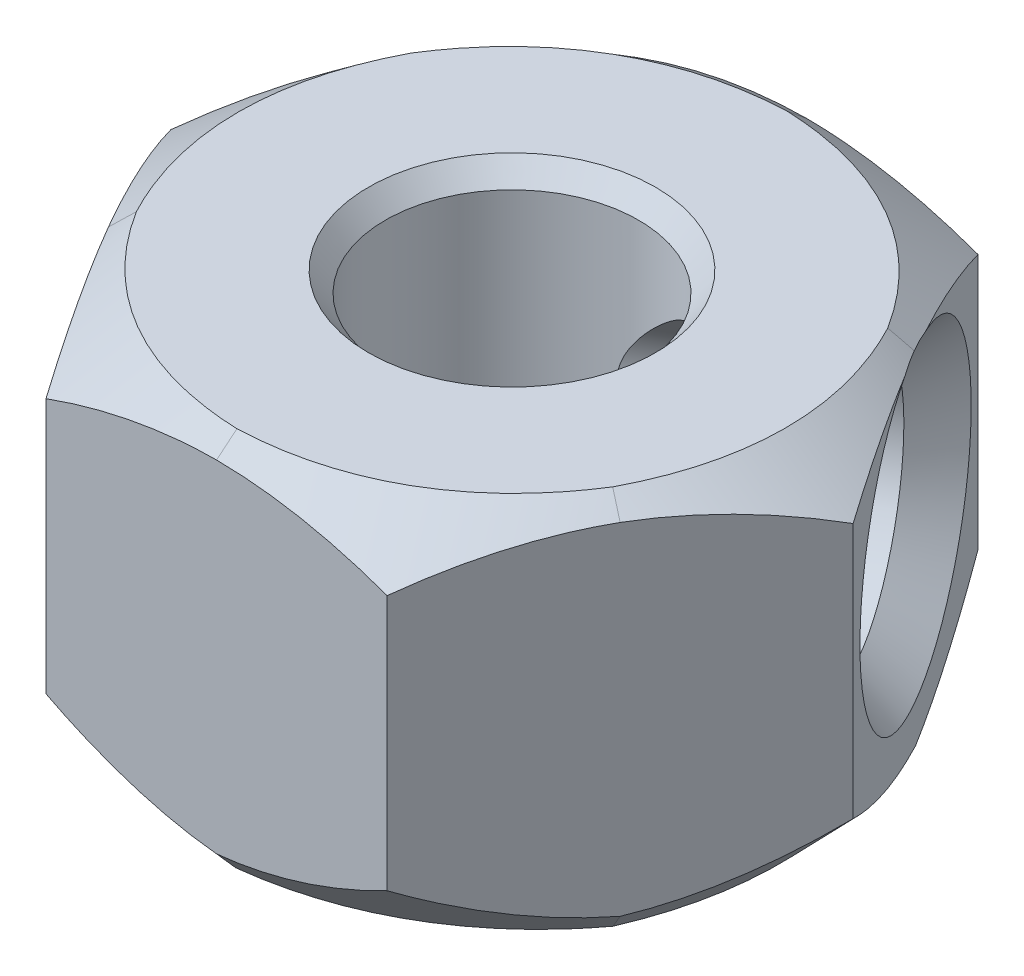
SolidWorks part; units mm, degrees
material "Ti-8Mn annealed sheet (SS)"
ref_plane "Front Plane" through (0, 0, 0) normal (0, 0, 1) x (1, 0, 0)
ref_plane "Top Plane" through (0, 0, 0) normal (0, 1, 0) x (1, 0, 0)
ref_plane "Right Plane" through (0, 0, 0) normal (1, 0, 0) x (0, 0, -1)
sketch "Sketch1" plane through (0, 0, 0) normal (0, 1, 0) x (1, 0, 0)
  line L1 (4.0415, 0) -> (2.0207, 3.5)
  line L2 (2.0207, 3.5) -> (-2.0207, 3.5)
  line L3 (-2.0207, 3.5) -> (-4.0415, 0)
  line L4 (-4.0415, 0) -> (-2.0207, -3.5)
  line L5 (-2.0207, -3.5) -> (2.0207, -3.5)
  line L6 (2.0207, -3.5) -> (4.0415, 0)
  circle A0 centre (0, 0) radius 3.5 construction
  circle A1 centre (0, 0) radius 1.5
  dimension "D1" = 7
  dimension "D2" = 3
extrude "Boss-Extrude1" add sketch "Sketch1" along normal blind 4.5
chamfer "Chamfer1" distance 0.2 angle 50 14 edges at (0, 0, 1.5) (3.0311, 0, -1.75) (0, 0, -3.5) (-3.0311, 0, -1.75) (-3.0311, 0, 1.75) (0, 0, 3.5) (3.0311, 0, 1.75) (0, 4.5, 1.5) (0, 4.5, 3.5) (-3.0311, 4.5, 1.75) (-3.0311, 4.5, -1.75) (0, 4.5, -3.5) (3.0311, 4.5, -1.75) (3.0311, 4.5, 1.75)
sketch "Sketch2" plane through (3.0311, 0, -1.75) normal (0.866, 0, -0.5) x (-0.5, 0, -0.866)
  circle A0 centre (0, 2.5192) radius 1.4
  dimension "D1" = 2.8
extrude "Cut-Extrude1" cut sketch "Sketch2" against normal blind 3
chamfer "Chamfer2" distance 0.4 angle 50 1 edges at (2.3311, 2.5192, -2.9624)
fillet "Fillet1" radius 5.5 12 edges at (-3.926, 0.1192, 0) (-1.963, 0.1192, -3.4) (1.963, 0.1192, -3.4) (3.926, 0.1192, 0) (1.963, 0.1192, 3.4) (-1.963, 0.1192, 3.4) (1.9519, 4.4, -3.3808) (-1.9519, 4.4, -3.3808) (-3.9038, 4.4, 0) (3.9038, 4.4, 0) (1.9519, 4.4, 3.3808) (-1.9519, 4.4, 3.3808)
